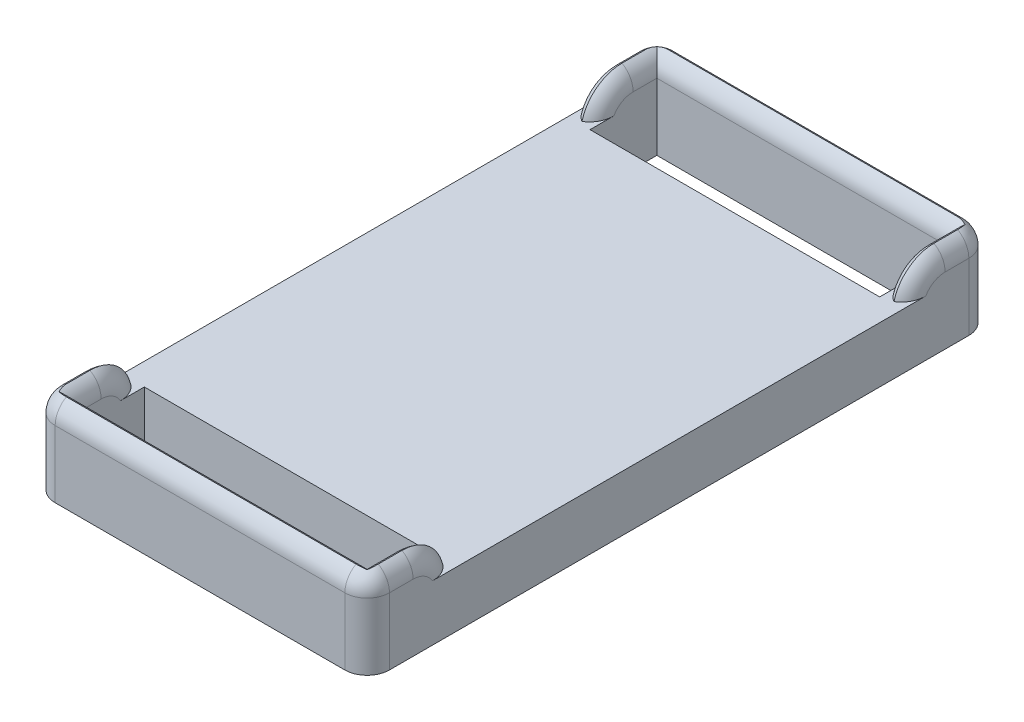
SolidWorks part; units mm, degrees
ref_plane "Front Plane" through (0, 0, 0) normal (0, 0, 1) x (1, 0, 0)
ref_plane "Top Plane" through (0, 0, 0) normal (0, 1, 0) x (1, 0, 0)
ref_plane "Right Plane" through (0, 0, 0) normal (1, 0, 0) x (0, 0, -1)
sketch "Sketch1" plane through (0, 0, 0) normal (0, 1, 0) x (1, 0, 0)
  line L0 (0, 10) -> (15, 10) construction
  line L2 (0, 0) -> (0, 20)
  line L4 (15, 0) -> (15, 20)
  line L5 (0, 20) -> (15, 20) construction
  line L6 (0, 20) -> (0, 24)
  line L7 (0, 24) -> (15, 24)
  line L8 (15, 20) -> (15, 24)
  line L9 (1, 20) -> (1, 23)
  line L10 (1, 23) -> (14, 23)
  line L11 (14, 20) -> (14, 23)
  line L12 (1, 20) -> (14, 20)
  line L13 (15, 0) -> (15, -4)
  line L14 (0, -4) -> (15, -4)
  line L15 (0, 0) -> (0, -4)
  line L16 (14, 0) -> (14, -3)
  line L17 (1, 0) -> (14, 0)
  line L18 (1, 0) -> (1, -3)
  line L19 (1, -3) -> (14, -3)
  dimension "D1" = 15
  dimension "D2" = 20
  dimension "D3" = 4
  dimension "D4" = 1
extrude "Boss-Extrude1" add sketch "Sketch1" along normal blind 4
sketch "Sketch2" plane through (0, 4, 0) normal (0, 1, 0) x (1, 0, 0)
  line L0 (15, -4) -> (15, 24) construction
  line L1 (15, 20) -> (0, 20)
  line L2 (15, 20) -> (15, 0)
  line L3 (15, 0) -> (0, 0)
  line L4 (0, 20) -> (0, 0)
  line L5 (0, 24) -> (0, -4) construction
  line L6 (15, 10) -> (0, 10) construction
  dimension "D1" = 20
extrude "Cut-Extrude1" cut sketch "Sketch2" against normal blind 1.5
fillet "Fillet1" radius 2 4 edges at (0.5, 4, 0) (14.5, 4, 0) (14.5, 4, -20) (0.5, 4, -20)
fillet "Fillet2" radius 1 24 edges at (14, 3.5811, 0.7117) (15, 3.5811, 0.7117) (0, 3.5811, 0.7117) (1, 3.5811, 0.7117) (1, 3.5811, -20.7117) (0, 3.5811, -20.7117) (15, 3.5811, -20.7117) (14, 3.5811, -20.7117) (7.5, 4, 3) (14, 4, 2.4682) (15, 4, 2.9682) (7.5, 4, 4) (0, 4, 2.9682) (1, 4, 2.4682) (7.5, 4, -23) (1, 4, -22.4682) (0, 4, -22.9682) (7.5, 4, -24) (15, 4, -22.9682) (14, 4, -22.4682) (0, 2, -24) (15, 2, -24) (15, 2, 4) (0, 2, 4)
